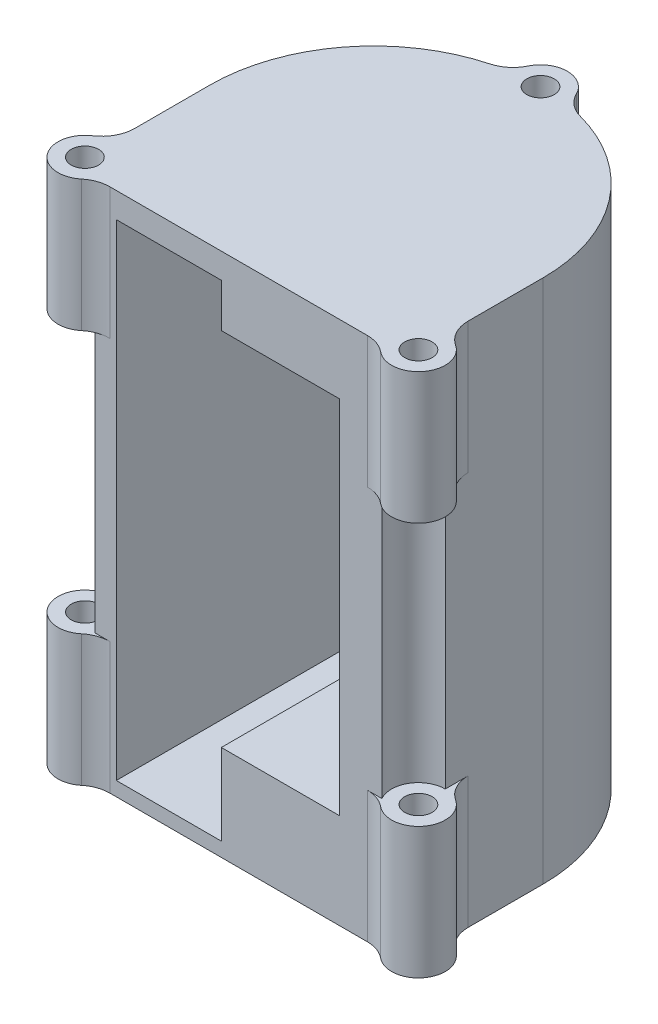
SolidWorks part; units mm, degrees
material "PLA"
ref_plane "Front Plane" through (0, 0, 0) normal (0, 0, 1) x (1, 0, 0)
ref_plane "Top Plane" through (0, 0, 0) normal (0, 1, 0) x (1, 0, 0)
ref_plane "Right Plane" through (0, 0, 0) normal (1, 0, 0) x (0, 0, -1)
sketch "Sketch1" plane through (0, 0, 0) normal (0, 1, 0) x (1, 0, 0)
  circle A0 centre (0, 0) radius 38.1
  dimension "D1" = 76.2
extrude "Bulkhead Body" add sketch "Sketch1" along normal blind 12.7 contours A0
sketch "Sketch2" plane through (0, 12.7, 0) normal (0, 1, 0) x (1, 0, 0)
  line L0 (0, 38.1) -> (0, 0)
  line L1 (0, 0) -> (-38.1, 0)
  circle A0 centre (0, 0) radius 38.1 construction
  circle A5 centre (0, 29.337) radius 1.5875
  circle A6 centre (25.4066, -14.5685) radius 1.5875
  circle A7 centre (-25.32, -14.6185) radius 1.5875
  point P15 (0.0289, 0.05)
  point P17 (0, 0)
  dimension "D2" = 3.175
  dimension "D1" = 8.763
  dimension "D3" = 3
extrude "Cut-Extrude1" cut sketch "Sketch2" against normal up to surface (12.7 mm away) contours A6 | A7 | L0 A5 | L0 A5 region at (0.6738, 12.7, -29.337) region at (-0.6738, 12.7, -29.337) region at (25.4066, 12.7, 14.5685) region at (-25.32, 12.7, 14.6185) up to face at (0, 0, 38.1)
sketch "Sketch3" plane through (0, 0, 0) normal (0, -1, 0) x (-1, 0, 0)
  line L0 (0, 0) -> (0, 29.337)
  line L1 (0, 0) -> (-25.4066, -14.6685)
  line L2 (0, 0) -> (25.4066, -14.6685)
  line L11 (25.4066, -14.6685) -> (0, 29.337)
  line L16 (-25.4066, -14.6685) -> (0, 29.337)
  line L17 (25.4066, -14.6685) -> (-25.4066, -14.6685)
  line L18 (25.4066, -14.6685) -> (25.4066, 4.337)
  line L19 (0.4066, 29.337) -> (0, 29.337)
  line L20 (-25.4066, -14.6685) -> (-25.4066, 4.337)
  line L21 (25.4066, -16.6685) -> (-25.4066, -16.6685)
  circle A0 centre (0, 0) radius 38
  circle A12 centre (25.4066, -14.6685) radius 1.5875
  circle A13 centre (-25.4066, -14.6685) radius 1.5875
  circle A14 centre (0, 29.337) radius 1.5875
  circle A15 centre (0, 29.337) radius 2.0875
  circle A16 centre (-25.4066, -14.6685) radius 2.0875
  circle A17 centre (25.4066, -14.6685) radius 2.0875
  circle A18 centre (25.4066, -14.6685) radius 4.0875
  circle A19 centre (-25.4066, -14.6685) radius 4.0875
  circle A20 centre (0, 29.337) radius 4.0875
  arc A21 (0.4066, 29.337) -> (25.4066, 4.337) centre (0.4066, 4.337) cw
  arc A22 (-0.4066, 29.337) -> (-25.4066, 4.337) centre (-0.4066, 4.337) ccw
  point P23 (-18, 33.4664)
  dimension "D7" = 0.5
  dimension "D1" = 25
  dimension "D2" = 2
  dimension "D4" = 3
  dimension "D8" = 2
extrude "Boss-Extrude1" add sketch "Sketch3" along normal blind 80 separate body contours L21 A18 L18 A17 | L18 A18 L11 A17 | L11 A18 L2 A17 | L2 A18 L17 A17 | L17 A18 L21 A17 | A19 L21 A18 L17 | A19 L17 A18 L2 L1 | A20 L0 L2 A18 L11 | A21 A20 L11 A18 L18 | A20 L16 A19 L1 L0 | A20 A22 L20 A19 L16 | L1 A19 L16 A16 | L17 A19 L1 A16 | L21 A19 L17 A16 | L20 A19 L21 A16 | L16 A19 L20 A16 | A21 A15 L11 A20 | L0 A20 L11 A15 | L16 A20 L0 A15 | A15 A22 A20 L16 | A22 A15 A21 A20 region at (8.3816, 0, -4.8391) region at (0, 0, 9.6782) region at (-8.3816, 0, -4.8391) region at (0.8176, 0, -26.2856) region at (-0.8176, 0, -26.2856) region at (22.3551, 0, 13.8509) region at (23.1728, 0, 12.4347) region at (-23.1728, 0, 12.4347) region at (-22.3551, 0, 13.8509) region at (2.6094, 0, -27.7411) region at (16.217, 0, -11.7236) region at (-16.217, 0, -11.7236) region at (-2.6094, 0, -27.7411) region at (22.6304, 0, 15.7258) region at (0, 0, 15.6725) region at (24.589, 0, 11.6171) region at (-24.589, 0, 11.6171) region at (-22.6304, 0, 15.7258) region at (0.1326, 0, -33.3297) region at (28.8372, 0, 16.6774) region at (-28.2177, 0, 11.8574)
delete or keep bodies "Body-Delete/Keep 1" type delete bodies bodies 103
sketch "Sketch4" plane through (0, 0, 16.6685) normal (0, 0, 1) x (1, 0, 0)
  line L11 (15.3798, -10.4858) -> (-2.6202, -10.4858)
  line L12 (15.3798, -10.4858) -> (15.3798, -65.4858)
  line L13 (15.3798, -65.4858) -> (-2.6202, -65.4858)
  line L15 (-2.6202, -10.4858) -> (-2.6202, -65.4858)
  line L17 (-2.6202, -3.8424) -> (-18.6202, -3.8424)
  line L19 (-2.6202, -3.8424) -> (-2.6202, -77.8424)
  line L20 (-2.6202, -77.8424) -> (-18.6202, -77.8424)
  line L21 (-18.6202, -3.8424) -> (-18.6202, -77.8424)
  dimension "D1" = 18
  dimension "D2" = 55
  dimension "D3" = 16
  dimension "D4" = 74
ref_plane "Plane1" through (0, -40, 0) normal (0, -1, 0) x (-1, 0, 0)
sketch "Sketch5" plane through (0, -40, 0) normal (0, -1, 0) x (-1, 0, 0)
  circle A0 centre (25.4066, -14.6685) radius 4.0875
  circle A1 centre (-25.4066, -14.6685) radius 4.0875
  circle A2 centre (0, 29.337) radius 4.0875
extrude "Cut-Extrude4" cut sketch "Sketch5" along normal offset from surface 20 and the other way offset from surface 20 up to face at (0, -80, -31.4245) other way up to face at (0, 0, -31.4245)
fillet "Fillet1" radius 5 12 edges at (-25.4066, -10, 10.581) (-25.4066, -70, 10.581) (25.4066, -10, 10.581) (25.4066, -70, 10.581) (21.8418, -70, 16.6685) (21.8418, -10, 16.6685) (-21.8418, -10, 16.6685) (-21.8418, -70, 16.6685) (-4.0785, -10, -29.0659) (-4.0785, -70, -29.0659) (4.0785, -10, -29.0659) (4.0785, -70, -29.0659)
extrude "Cut-Extrude5" cut sketch "Sketch4" against normal blind 34 contours L17 L21 L20 L19 L15 region at (-10.6202, -40.8424, 16.6685)
extrude "Cut-Extrude6" cut sketch "Sketch4<5>" against normal blind 40 contours L13 L15 L11 L12
sketch "Sketch4<5>" plane through (0, 0, 16.6685) normal (0, 0, 1) x (1, 0, 0) same geometry as "Sketch4"
